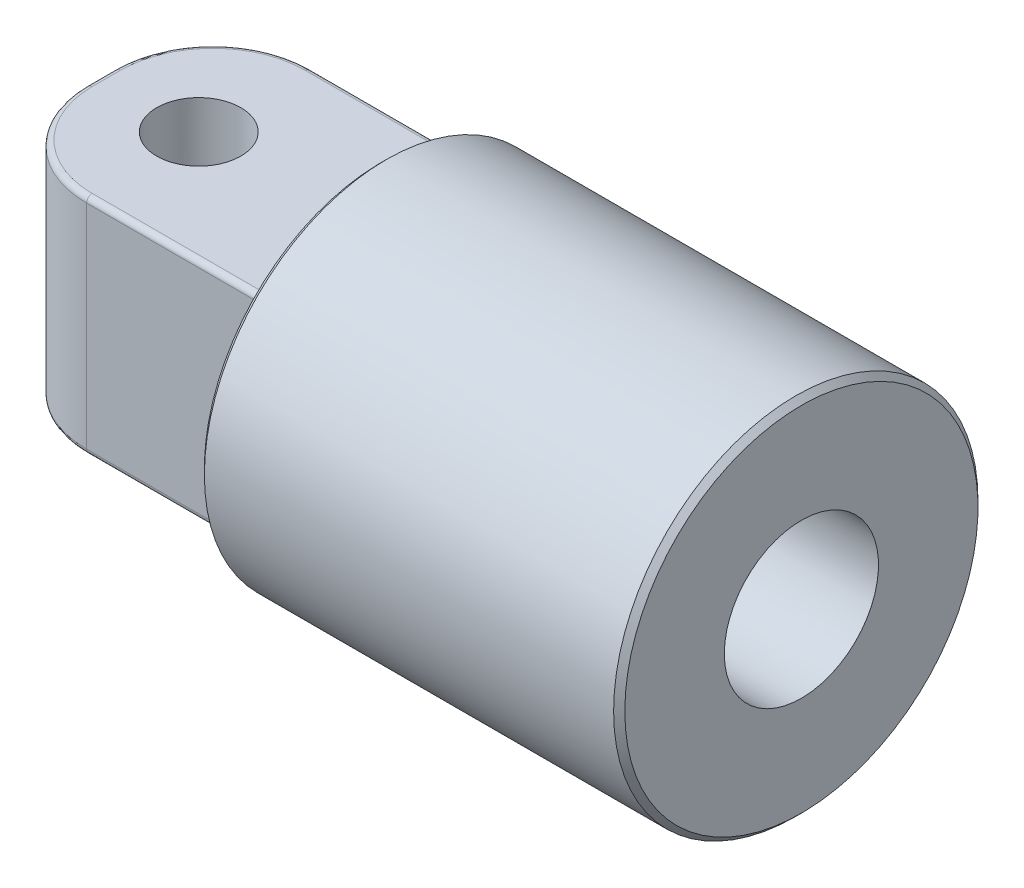
SolidWorks part; units mm, degrees
ref_plane "Front Plane" through (0, 0, 0) normal (0, 0, 1) x (1, 0, 0)
ref_plane "Top Plane" through (0, 0, 0) normal (0, 1, 0) x (1, 0, 0)
ref_plane "Right Plane" through (0, 0, 0) normal (1, 0, 0) x (0, 0, -1)
sketch "Sketch1" plane through (0, 0, 0) normal (0, 0, 1) x (1, 0, 0)
  line L0 (0, 0) -> (15, 0) construction
  line L1 (0, 6.5) -> (15, 6.5)
  line L2 (15, 6.5) -> (15, 2.75)
  line L3 (15, 2.75) -> (0, 2.75)
  line L4 (0, 2.75) -> (0, 6.5)
  dimension "D1" = 6.5
  dimension "D2" = 15
  dimension "D3" = 2.75
revolve "Revolve1" add sketch "Sketch1" angle 360 about L0
sketch "Sketch3" plane through (0, 0, 0) normal (-1, 0, 0) x (0, 0, 1)
  line L0 (-6.5, 0) -> (6.5, 0) construction
  line L1 (0, 6.5) -> (0, -6.5) construction
  line L3 (-4, -4) -> (4, -4)
  line L4 (-4, -4) -> (-4, 4)
  line L5 (-4, 4) -> (4, 4)
  line L6 (4, -4) -> (4, 4)
  line L7 (-4, -4) -> (4, 4) construction
  line L8 (-4, 4) -> (4, -4) construction
  circle A0 centre (0, 0) radius 6.5 construction
  point P7 (0, 0)
  dimension "D1" = 8
  dimension "D2" = 8
extrude "Boss-Extrude1" add sketch "Sketch3" along normal blind 10
fillet "Fillet1" radius 3.5 2 edges at (-10, 0, 4) (-10, 0, -4)
sketch "Sketch4" plane through (0, -4, 0) normal (0, -1, 0) x (1, 0, 0)
  circle A0 centre (-6.5, 0) radius 1.5
  dimension "D1" = 3
extrude "Cut-Extrude1" cut sketch "Sketch4" against normal through all
sketch "Sketch5" plane through (0, 0, -4) normal (0, 0, -1) x (-1, 0, 0)
  line L0 (0, 0) -> (11.9453, 0) construction
  line L1 (0, 4) -> (0, -4) construction
  line L2 (2, 1.775) -> (10.8938, 1.775)
  line L3 (2, 1.775) -> (2, -1.775)
  line L4 (2, -1.775) -> (10.8938, -1.775)
  line L5 (10.8938, 1.775) -> (10.8938, -1.775)
  dimension "D1" = 3.55
  dimension "D2" = 2
extrude "Cut-Extrude2" cut sketch "Sketch5" against normal blind 6
chamfer "Chamfer1" distance 0.2 angle 45 2 edges at (0, 0, 6.5) (15, 0, 6.5)
fillet "Fillet3" radius 0.2 29 edges at (-9.6623, 0, 2) (-3.25, -4, 4) (-8.9749, -4, 2.9749) (-10, -4, 0) (-8.9749, -4, -2.9749) (-3.25, 4, 4) (-8.9749, 4, 2.9749) (-10, 4, 0) (-8.9749, 4, -2.9749) (-5.8311, 1.775, 2) (-2, 1.775, -1) (-4.25, 1.775, -4) (-8.9749, 1.775, -2.9749) (-10, 1.775, 0) (-9.9145, 1.775, 1.2688) (-6.5, -1.775, -1.5) (-10, -1.775, 0) (-8.9749, -1.775, -2.9749) (-4.25, -1.775, -4) (-2, -1.775, -1) (-5.8311, -1.775, 2) (-9.9145, -1.775, 1.2688) (-2, 0, -4) (-3.25, -4, -4) (-3.25, 4, -4) (0, 4, 0) (0, 0, -4) (0, -4, 0) (0, 0, 4)
sketch "Sketch7" plane through (0, 4, 0) normal (0, 1, 0) x (1, 0, 0)
  line L0 (-0.2, 0) -> (-10.8611, 0) construction
  line L1 (-0.2, -3.8) -> (-0.2, 3.8) construction
